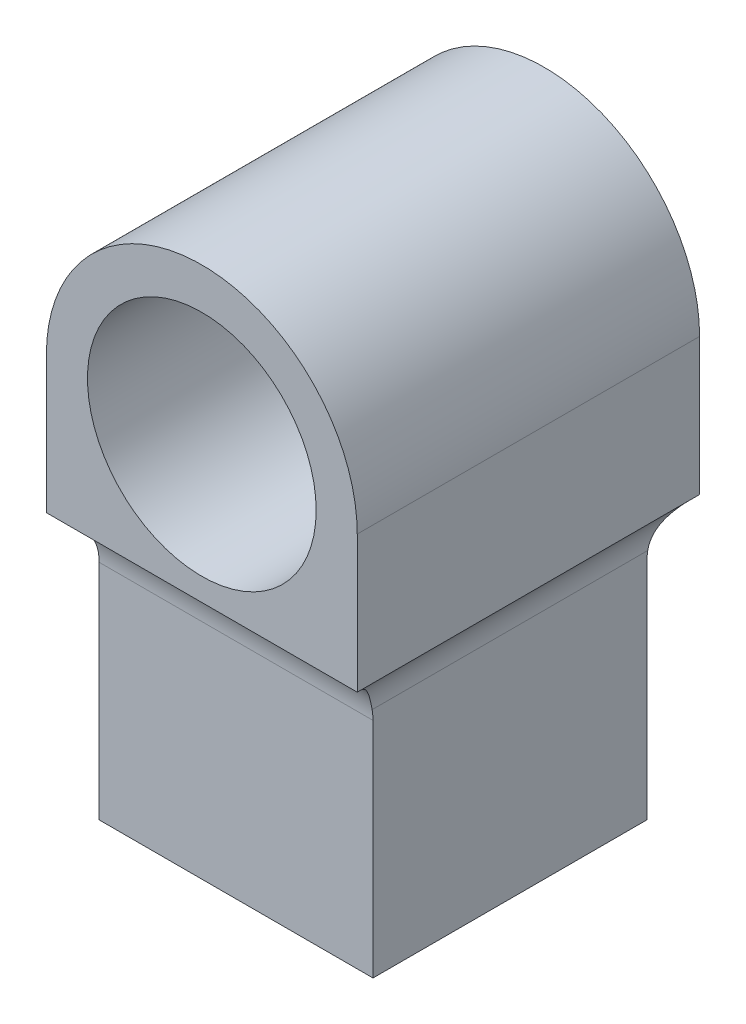
SolidWorks part; units mm, degrees
ref_plane "Alzado" through (0, 0, 0) normal (0, 0, 1) x (1, 0, 0)
ref_plane "Planta" through (0, 0, 0) normal (0, 1, 0) x (1, 0, 0)
ref_plane "Vista lateral" through (0, 0, 0) normal (1, 0, 0) x (0, 0, -1)
sketch "Croquis1" plane through (0, 0, 0) normal (0, 0, 1) x (1, 0, 0)
  line L0 (0, 0) -> (0, -10) construction
  line L1 (-11.35, -10) -> (11.35, -10)
  line L2 (-11.35, -10) -> (-11.35, 0)
  line L3 (11.35, -10) -> (11.35, 0)
  circle A0 centre (0, 0) radius 8.35
  arc A1 (11.35, 0) -> (-11.35, 0) centre (0, 0) ccw
  point P8 (0, -10)
  dimension "D1" = 16.7
  dimension "D2" = 3
  dimension "D3" = 10
extrude "Saliente-Extruir1" add sketch "Croquis1" against normal mid plane 25
ref_plane "Plano1" through (0, -10, 0) normal (0, -1, 0) x (-1, 0, 0)
sketch "Croquis3" plane through (0, -10, 0) normal (0, -1, 0) x (-1, 0, 0)
  line L1 (-10, -10) -> (10, -10)
  line L2 (-10, -10) -> (-10, 10)
  line L3 (-10, 10) -> (10, 10)
  line L4 (10, -10) -> (10, 10)
  line L5 (-10, -10) -> (10, 10) construction
  line L6 (-10, 10) -> (10, -10) construction
  circle A0 centre (0, 0) radius 8.35
  dimension "D1" = 16.7
  dimension "D2" = 10
  dimension "D3" = 10
extrude "Saliente-Extruir2" add sketch "Croquis3" along normal blind 20
fillet "Redondeo1" radius 4 4 edges at (0, -10, -10) (10, -10, 0) (0, -10, 10) (-10, -10, 0)
